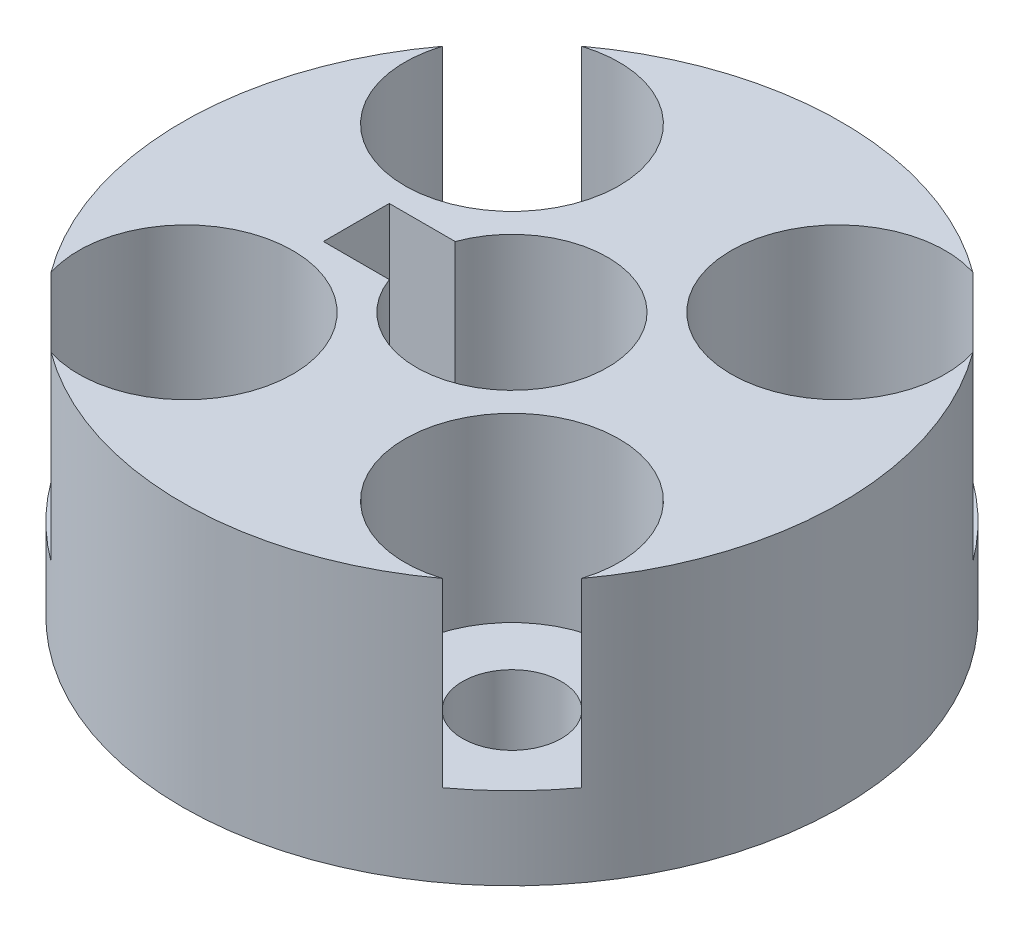
SolidWorks part; units mm, degrees
ref_plane "Front Plane" through (0, 0, 0) normal (0, 0, 1) x (1, 0, 0)
ref_plane "Top Plane" through (0, 0, 0) normal (0, 1, 0) x (1, 0, 0)
ref_plane "Right Plane" through (0, 0, 0) normal (1, 0, 0) x (0, 0, -1)
sketch "Sketch1" plane through (0, 0, 0) normal (0, 1, 0) x (1, 0, 0)
  line L1 (-4.9497, -4.9497) -> (4.9497, -4.9497) construction
  line L2 (-4.9497, -4.9497) -> (-4.9497, 4.9497) construction
  line L3 (-4.9497, 4.9497) -> (4.9497, 4.9497) construction
  line L4 (4.9497, -4.9497) -> (4.9497, 4.9497) construction
  line L5 (-4.9497, -4.9497) -> (4.9497, 4.9497) construction
  line L6 (-4.9497, 4.9497) -> (4.9497, -4.9497) construction
  line L9 (-4.9497, 0) -> (4.9497, 0) construction
  line L14 (-4.7221, 1) -> (-4.7221, -1)
  line L18 (-4.7221, -1) -> (-2.7221, -1)
  line L19 (-2.7221, 1) -> (-4.7221, 1)
  line L20 (0, 6.736) -> (0, -6.736) construction
  arc A0 (8.0456, 5.9387) -> (5.9387, 8.0456) centre (0, 0) ccw
  circle A1 centre (-4.9497, 4.9497) radius 1.5
  circle A2 centre (4.9497, 4.9497) radius 1.5
  circle A3 centre (4.9497, -4.9497) radius 1.5
  circle A4 centre (-4.9497, -4.9497) radius 1.5
  arc A6 (5.9387, 8.0456) -> (8.0456, 5.9387) centre (4.9497, 4.9497) ccw
  arc A7 (8.0456, -5.9387) -> (5.9387, -8.0456) centre (4.9497, -4.9497) ccw
  arc A8 (-5.9387, -8.0456) -> (-8.0456, -5.9387) centre (-4.9497, -4.9497) ccw
  arc A9 (-8.0456, 5.9387) -> (-5.9387, 8.0456) centre (-4.9497, 4.9497) ccw
  arc A11 (-2.7221, -1) -> (-2.7221, 1) centre (0, 0) ccw
  arc A12 (5.9387, 8.0456) -> (8.0456, 5.9387) centre (0, 0) ccw
  dimension "D2" = 3
  dimension "D3" = 3
  dimension "D4" = 3
  dimension "D5" = 3
  dimension "D6" = 20
  dimension "D7" = 6.5
  dimension "D8" = 6.5
  dimension "D9" = 6.5
  dimension "D10" = 6.5
  dimension "D14" = 2.9
  dimension "D1" = 14
  dimension "D11" = 2
  dimension "D12" = 2
extrude "Boss-Extrude1" add sketch "Sketch1" along normal blind 2.5 contours A9 A0 A8 A7 A6 A11 L18 L14 L19 | A0 A9 A1 | A0 A6 A2 | A0 A7 A3 | A0 A8 A4 region at (2.7167, 0, -2.7167) region at (9.7172, 0, 0) region at (7.0061, 0, 7.0061) region at (-2.7167, 0, -2.7167) region at (-7.0061, 0, 7.0061)
extrude "Boss-Extrude5" add sketch "Sketch1<14>" along normal blind 8 contours A7 A12 A6 A9 A8 A11 L18 L14 L19 region at (9.7172, 0, 0)
sketch "Sketch1<14>" plane through (0, 0, 0) normal (0, 1, 0) x (1, 0, 0) same geometry as "Sketch1"
